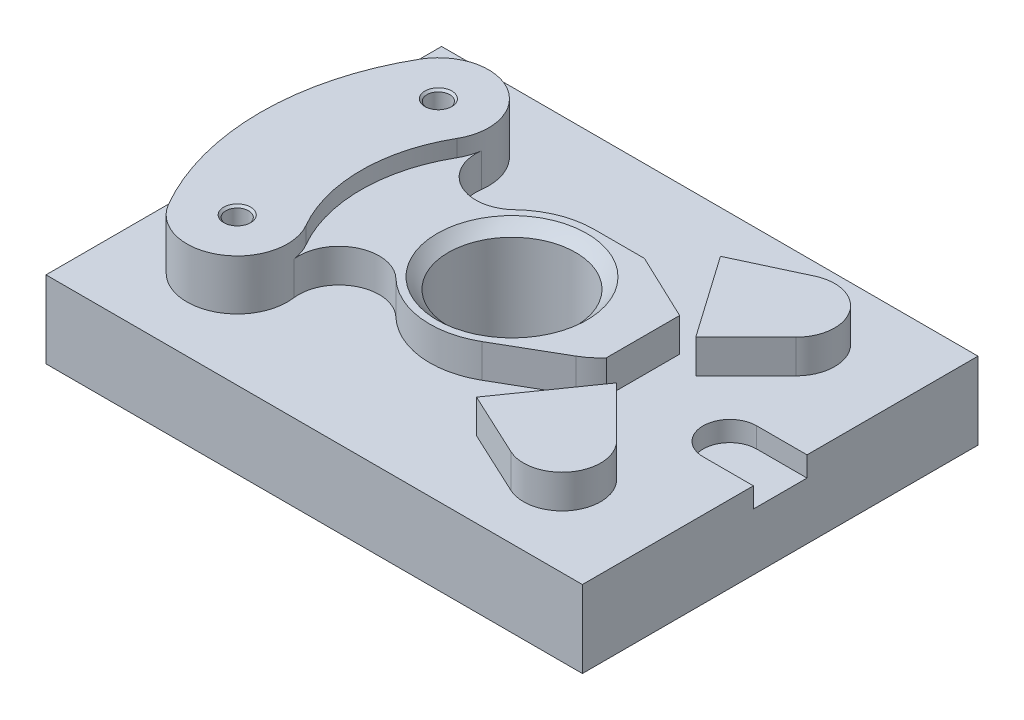
SolidWorks part; units mm, degrees
ref_plane "前视基准面" through (0, 0, 0) normal (0, 0, 1) x (1, 0, 0)
ref_plane "上视基准面" through (0, 0, 0) normal (0, 1, 0) x (1, 0, 0)
ref_plane "右视基准面" through (0, 0, 0) normal (1, 0, 0) x (0, 0, -1)
other "Configuration Table"
sketch "草图1" plane through (0, 0, 0) normal (0, 1, 0) x (1, 0, 0)
  line L0 (-51.9615, 30) -> (0, 0) construction
  line L1 (-80, -59) -> (80, -59)
  line L2 (-80, -59) -> (-80, 59)
  line L3 (-80, 59) -> (80, 59)
  line L4 (80, -59) -> (80, 59)
  line L5 (-80, -59) -> (80, 59) construction
  line L6 (-80, 59) -> (80, -59) construction
  line L7 (0, 0) -> (-60, 0) construction
  arc A0 (-51.9615, -30) -> (-51.9615, 30) centre (0, 0) cw construction
  arc A1 (-64.9519, 37.5) -> (-64.9519, -37.5) centre (0, 0) ccw
  arc A2 (-38.9711, 22.5) -> (-38.9711, -22.5) centre (0, 0) ccw
  arc A3 (-38.9711, 22.5) -> (-64.9519, 37.5) centre (-51.9615, 30) ccw
  arc A4 (-64.9519, -37.5) -> (-38.9711, -22.5) centre (-51.9615, -30) ccw
  point P0 (0, 0)
  point P9 (-60, 0)
  dimension "D3" = 30
  dimension "D5" = 60
  dimension "D1" = 160
  dimension "D2" = 118
  dimension "D4" = 30
extrude "凸台-拉伸1" add sketch "草图1" along normal blind 23 contours L2 L1 L4 L3
extrude "凸台-拉伸2" add sketch "草图1<3>" along normal blind 38 contours A1 A4 A2 A3 region at (-55.841, 0, 0)
sketch "草图1<3>" plane through (0, 0, 0) normal (0, 1, 0) x (1, 0, 0) same geometry as "草图1"
hole_wizard "M8 螺纹孔2" positions "草图4" profile "草图5" tap size "M8" standard "GB"
sketch "草图4" plane through (0, 38, 0) normal (0, 1, 0) x (1, 0, 0)
  point P0 (-51.9615, 30)
  point P3 (-51.9615, -30)
sketch "草图5" plane through (-51.9615, 38, -30) normal (1, 0, 0) x (0, 0, 1)
  line L0 (0, 0) -> (0, 20)
  line L1 (0, 20) -> (3.4, 17.9571)
  line L2 (3.4, 17.9571) -> (3.4, 0.625)
  line L3 (3.4, 0.625) -> (4.025, 0)
  line L5 (4.025, 0) -> (0, 0)
  line L6 (-3.4, 0.625) -> (-4.025, 0) construction
  line L10 (0, 20) -> (-3.4, 17.9571) construction
  line L11 (0, -6.35) -> (0, 107.95) construction
  dimension "螺纹孔钻头直径" = 6.8
  dimension "螺纹孔钻头深度" = 20
  dimension "近端锥形沉头孔直径" = 8.05
  dimension "近端锥形沉头孔角度" = 90
  dimension "导头角度" = 118
cosmetic thread "孔螺纹线3" parameters "D1"=16, "D2"=8
cosmetic thread "孔螺纹线4" parameters "D1"=16, "D2"=8
sketch "草图6" plane through (0, 23, 0) normal (0, 1, 0) x (1, 0, 0)
  line L0 (0, 0) -> (-60, 0) construction
  line L1 (0, 0) -> (-60, 0) construction
  line L2 (0, 24.5) -> (15, 24.5)
  line L3 (15, 24.5) -> (35, 15)
  line L4 (35, 15) -> (35, 0)
  line L5 (35, -6.8779) -> (35, 0)
  line L6 (12.25, -21.2176) -> (30, -10.9697)
  line L7 (0, 0) -> (0, -49.0521) construction
  circle A0 centre (0, 0) radius 24.5
  arc A1 (-16.9166, 17.7223) -> (-37.0953, 28.0014) centre (-25.2023, 26.4026) cw
  arc A2 (-38.9711, 22.5) -> (-64.9519, 37.5) centre (-51.9615, 30) ccw construction
  arc A3 (-16.9166, -17.7223) -> (-37.0953, -28.0014) centre (-25.2023, -26.4026) ccw
  arc A4 (30, -10.9697) -> (35, -6.8779) centre (20, 6.3509) ccw
  arc A8 (-64.9519, 37.5) -> (-64.9519, -37.5) centre (0, 0) ccw
  arc A9 (-64.9519, -37.5) -> (-38.9711, -22.5) centre (-51.9615, -30) ccw
  arc A10 (-38.9711, 22.5) -> (-38.9711, -22.5) centre (0, 0) ccw
  arc A11 (-38.9711, 22.5) -> (-64.9519, 37.5) centre (-51.9615, 30) ccw
  arc A13 (-37.0953, -28.0014) -> (-38.9711, -22.5) centre (-51.9615, -30) ccw
  arc A14 (-38.9711, 22.5) -> (-38.9711, -22.5) centre (0, 0) ccw
  arc A15 (-38.9711, 22.5) -> (-37.0953, 28.0014) centre (-51.9615, 30) ccw
  point P2 (35, -3.4877)
  point P25 (25.7348, -10.8856)
  point P31 (35, -1.4678)
  point P32 (35, -4.8352)
  point P33 (35, -6.6635)
  arc M7 (-38.9711, -22.5) -> (-64.9519, -37.5) centre (-51.9615, -30) cw
  arc M9 (-64.9519, 37.5) -> (-38.9711, 22.5) centre (-51.9615, 30) cw
  arc M10 (-38.9711, 22.5) -> (-38.9711, -22.5) centre (0, 0) ccw
  dimension "D1" = 49
  dimension "D2" = 0
  dimension "D3" = 12
  dimension "D8" = 5
  dimension "D6" = 20
  dimension "D4" = 15
  dimension "D5" = 15
  dimension "D7" = 60
  dimension "D9" = 35
extrude "凸台-拉伸3" add sketch "草图6" along normal blind 10 contours A3 A0 A1 M9 M10 M7 | A0 | L6 A4 L5 L4 L3 L2 A0 region at (26.1844, 23, -5.7479) region at (0, 23, 0) region at (-34.0342, 23, 0)
sketch "草图8" plane through (0, 23, 0) normal (0, 1, 0) x (1, 0, 0)
  line L0 (0, 0) -> (63.973, 44.7944) construction
  line L1 (25.8007, 36.3775) -> (43.008, 11.8029)
  line L2 (25.8007, 36.3775) -> (44.9799, 45.3209)
  line L3 (43.008, 11.8029) -> (57.9717, 26.7666)
  line L4 (0, 0) -> (99.5576, 0) construction
  line L5 (43.008, -11.8029) -> (57.9717, -26.7666)
  line L6 (25.8007, -36.3775) -> (44.9799, -45.3209)
  line L7 (25.8007, -36.3775) -> (43.008, -11.8029)
  circle A0 centre (0, 0) radius 42 construction
  arc A1 (57.9717, 26.7666) -> (44.9799, 45.3209) centre (49.84, 34.8983) ccw
  arc A2 (57.9717, -26.7666) -> (44.9799, -45.3209) centre (49.84, -34.8983) cw
  point P7 (34.4044, 24.0902)
  point P15 (34.4044, -24.0902)
  dimension "D1" = 84
  dimension "D2" = 23
  dimension "D3" = 30
  dimension "D4" = 80
  dimension "D5" = 35
extrude "凸台-拉伸4" add sketch "草图8" along normal blind 10
sketch "草图9" plane through (0, 33, 0) normal (0, 1, 0) x (1, 0, 0)
  circle A0 centre (0, 0) radius 19
  dimension "D1" = 38
extrude "切除-拉伸1" cut sketch "草图9" against normal through all
sketch "草图10" plane through (0, 0, 0) normal (0, 0, 1) x (1, 0, 0)
  line L0 (19, 33) -> (-19, 33) construction
  line L1 (0, 0) -> (0, 53) construction
  line L2 (0, 23) -> (0, 83)
  circle A0 centre (0, 53) radius 30
  dimension "D1" = 60
  dimension "D2" = 20
revolve "切除-旋转5" cut sketch "草图10" angle 360 about L2 region at (12.7324, 53, 0)
sketch "草图11" plane through (0, 23, 0) normal (0, 1, 0) x (1, 0, 0)
  line L0 (95, 0) -> (65, 0) construction
  line L1 (80, -59) -> (80, 59) construction
  line L2 (95, -8) -> (65, -8)
  line L3 (95, 8) -> (65, 8)
  arc A0 (95, -8) -> (95, 8) centre (95, 0) ccw
  arc A1 (65, 8) -> (65, -8) centre (65, 0) ccw
  point P5 (80, 0)
  point P10 (80, 0)
  point P11 (95, 9.499)
  dimension "D2" = 8
  dimension "D1" = 15
extrude "切除-拉伸2" cut sketch "草图11" against normal blind 6
